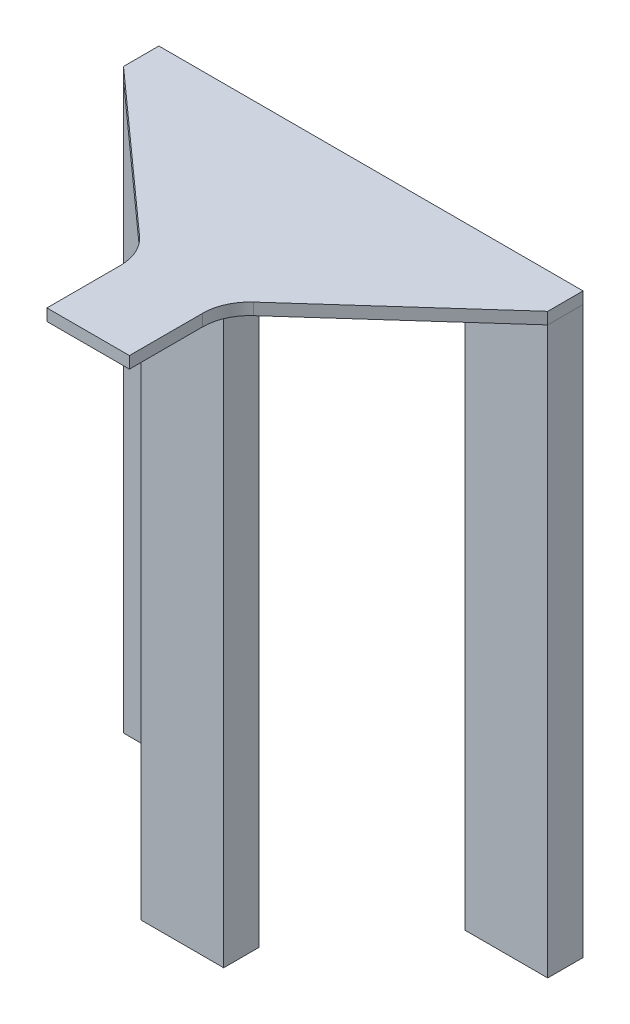
SolidWorks part; units mm, degrees
ref_plane "Front Plane" through (0, 0, 0) normal (0, 0, 1) x (1, 0, 0)
ref_plane "Top Plane" through (0, 0, 0) normal (0, 1, 0) x (1, 0, 0)
ref_plane "Right Plane" through (0, 0, 0) normal (1, 0, 0) x (0, 0, -1)
sketch "Sketch1" plane through (0, 0, 0) normal (0, 1, 0) x (1, 0, 0)
  line L0 (0, 304.8) -> (0, 139.7) construction
  line L1 (-228.6, 304.8) -> (228.6, 304.8)
  line L2 (-228.6, 304.8) -> (-228.6, 266.7)
  line L3 (-44.45, 0) -> (44.45, 0)
  line L4 (228.6, 304.8) -> (228.6, 266.7)
  line L5 (-228.6, 304.8) -> (-139.7, 304.8)
  line L6 (-228.6, 304.8) -> (-228.6, 266.7)
  line L7 (-228.6, 266.7) -> (-139.7, 266.7)
  line L8 (-139.7, 304.8) -> (-139.7, 266.7)
  line L9 (228.6, 304.8) -> (139.7, 304.8)
  line L10 (228.6, 304.8) -> (228.6, 266.7)
  line L11 (228.6, 266.7) -> (139.7, 266.7)
  line L12 (139.7, 304.8) -> (139.7, 266.7)
  line L13 (-44.45, 139.7) -> (44.45, 139.7)
  line L14 (-44.45, 139.7) -> (-44.45, 101.6)
  line L15 (-44.45, 101.6) -> (44.45, 101.6)
  line L16 (44.45, 139.7) -> (44.45, 101.6)
  line L17 (-139.7, 266.7) -> (-44.45, 139.7) construction
  line L18 (44.45, 139.7) -> (139.7, 266.7) construction
  line L19 (-228.6, 266.7) -> (-44.45, 101.6)
  line L20 (-44.45, 101.6) -> (-44.45, 0)
  line L21 (44.45, 101.6) -> (44.45, 0)
  line L22 (44.45, 101.6) -> (228.6, 266.7)
  point P1 (-49.5197, 70.8149)
  point P2 (-5.2403, 132.1659)
  point P19 (42.7735, 0)
  point P20 (0, 129.4985)
  point P21 (0, 276.2073)
  point P22 (-44.45, 100.1567)
  point P23 (-93.695, 261.8607)
  point P24 (-108.9201, 266.7)
  dimension "D1" = 38.1
  dimension "D2" = 88.9
  dimension "D3" = 101.6
  dimension "D4" = 127
  dimension "D5" = 457.2
extrude "Boss-Extrude1" add sketch "Sketch1" along normal blind 12.7 contours L16 L22 L11 L12 L1 L8 L7 L19 L14 L13 | L16 L13 L14 L15 | L8 L1 L2 L7 | L1 L12 L11 L4 | L21 L15 L20 L3 region at (-184.15, 0, -285.75) region at (0, 0, -224.9081) region at (184.15, 0, -285.75) region at (0, 0, -120.65) region at (0, 0, -50.8)
extrude "Boss-Extrude2" add sketch "Sketch1<3>" against normal blind 609.6 separate body contours L8 L1 L2 L7 | L16 L13 L14 L15 | L1 L12 L11 L4 region at (-184.15, 0, -285.75) region at (184.15, 0, -285.75) region at (0, 0, -120.65)
sketch "Sketch1<3>" plane through (0, 0, 0) normal (0, 1, 0) x (1, 0, 0) same geometry as "Sketch1"
fillet "Fillet1" radius 50.8 2 edges at (44.45, 6.35, -101.6) (-44.45, 6.35, -101.6)
